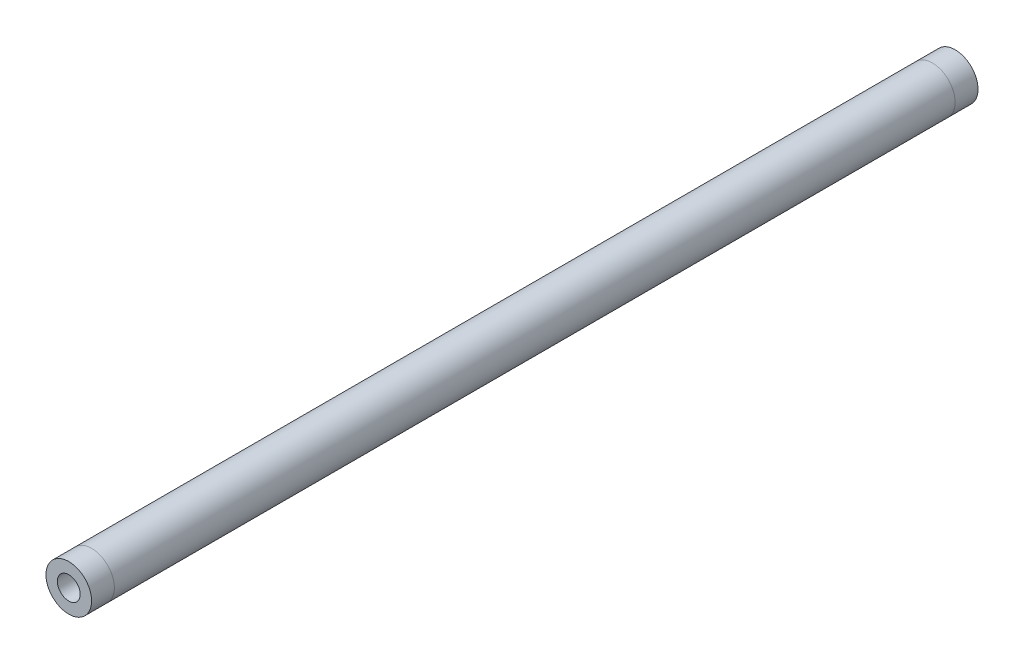
SolidWorks part; units mm, degrees
material "AISI 4130 Steel, normalized at 870C"
ref_plane "Front Plane" through (0, 0, 0) normal (0, 0, 1) x (1, 0, 0)
ref_plane "Top Plane" through (0, 0, 0) normal (0, 1, 0) x (1, 0, 0)
ref_plane "Right Plane" through (0, 0, 0) normal (1, 0, 0) x (0, 0, -1)
sketch "Axis" plane through (0, 0, 0) normal (1, 0, 0) x (0, 0, -1)
  line L0 (0, 0) -> (246.6988, 0) construction
  line L1 (246.6988, 0) -> (240.3488, 0)
  line L2 (246.6988, 0) -> (268.6063, 0) construction
  line L3 (0, 0) -> (-21.9075, 0) construction
  line L4 (-21.9075, 0) -> (-95.3875, 0)
  point P4 (0, 0)
  point P5 (246.6988, 0)
  point P6 (240.3488, 0)
  dimension "D1" = 6.35
  dimension "D2" = 21.9075
  dimension "D3" = 21.9075
sketch "Sketch1" plane through (0, 0, 0) normal (0, 0, 1) x (1, 0, 0)
  circle A0 centre (0, 0) radius 6.35
  circle A1 centre (0, 0) radius 4.8768
  circle A2 centre (0, 0) radius 3.175
  dimension "D1" = 12.7
  dimension "D2" = 1.4732
  dimension "D3" = 6.35
extrude "Threaded insert 1-1" add sketch "Sketch1" against normal blind 6.35 contours A0 A1 | A1 A2 region at (-6.1704, 0, 0) region at (-4.7389, 0, 0)
extrude "Threaded insert 1-2" add sketch "Sketch1<3>" against normal blind 6.35 from surface contours A1 A2 region at (-4.7389, 0, 0) starting at face at (6.35, 0, -6.35)
sketch "Sketch1<3>" plane through (0, 0, 0) normal (0, 0, 1) x (1, 0, 0) same geometry as "Sketch1"
extrude "Tube extrude" add sketch "Sketch1<4>" against normal up to vertex (240.3488 mm away) from surface separate body contours A0 A1 region at (-6.1704, 0, 0) up to point (0, 0, -240.3488) starting at face at (4.8768, 0, -6.35)
sketch "Sketch1<4>" plane through (0, 0, 0) normal (0, 0, 1) x (1, 0, 0) same geometry as "Sketch1"
extrude "Threaded insert 2-1" add sketch "Sketch1<6>" along normal blind 6.35 from surface separate body contours A1 A2 region at (-4.7389, 0, 0) starting at face at (4.8768, 0, -240.3488)
sketch "Sketch1<6>" plane through (0, 0, 0) normal (0, 0, 1) x (1, 0, 0) same geometry as "Sketch1"
extrude "Threaded insert 2-2" add sketch "Sketch1<9>" against normal blind 6.35 from surface separate body contours A1 A2 | A0 A1 region at (-6.1704, 0, 0) region at (-4.7389, 0, 0) starting at face at (4.8768, 0, -240.3488)
sketch "Sketch1<9>" plane through (0, 0, 0) normal (0, 0, 1) x (1, 0, 0) same geometry as "Sketch1"
combine bodies "Combine1" operation type add bodies to combine 106 104
equation "\"Threaded insert outer thickness\"= .25"
equation "\"D1@Threaded insert 1-1\"=\"Threaded insert outer thickness\""
equation "\"D1@Threaded insert 2-2\"=\"Threaded insert outer thickness\""
equation "\"D1@Axis\" = \"Threaded insert outer thickness\""
